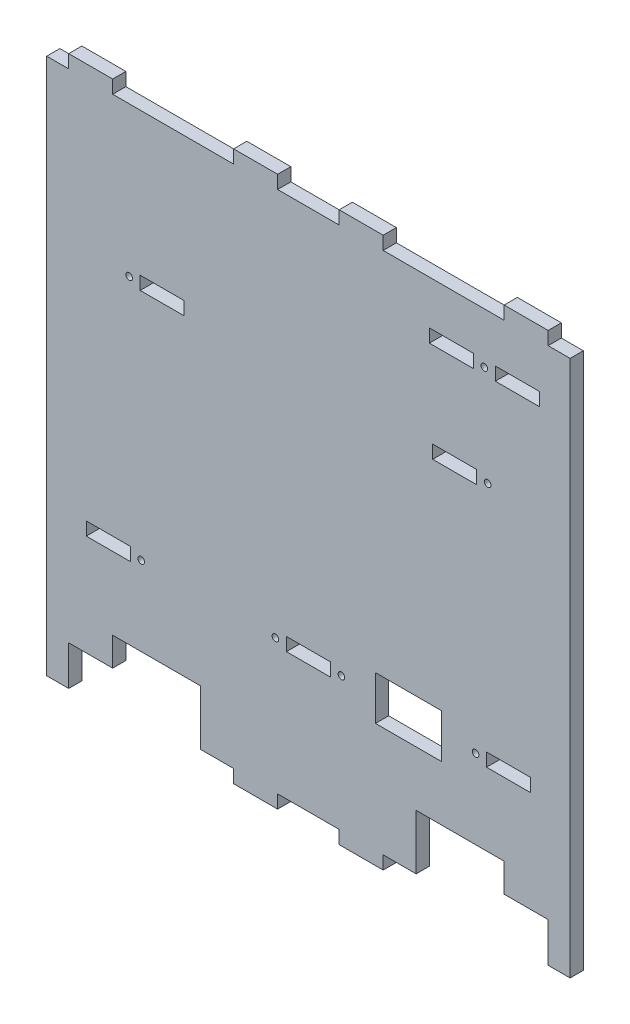
SolidWorks part; units mm, degrees
ref_plane "Plan de face" through (0, 0, 0) normal (0, 0, 1) x (1, 0, 0)
ref_plane "Plan de dessus" through (0, 0, 0) normal (0, 1, 0) x (1, 0, 0)
ref_plane "Plan de droite" through (0, 0, 0) normal (1, 0, 0) x (0, 0, -1)
sketch "Esquisse1" plane through (0, 0, 0) normal (0, 0, 1) x (1, 0, 0)
  line L0 (0, 139.6766) -> (0, -178.3461) construction
  line L1 (-109, 119) -> (109, 119)
  line L2 (-109, 119) -> (-109, -119)
  line L3 (-109, -119) -> (109, -119)
  line L4 (109, 119) -> (109, -119)
  line L5 (-101, -61) -> (-81, -61)
  line L6 (-101, -61) -> (-101, -55)
  line L7 (-101, -55) -> (-81, -55)
  line L8 (-81, -61) -> (-81, -55)
  line L9 (-10, -61) -> (10, -61)
  line L10 (-10, -61) -> (-10, -55)
  line L11 (-10, -55) -> (10, -55)
  line L12 (10, -61) -> (10, -55)
  line L13 (81, -61) -> (101, -61)
  line L14 (81, -61) -> (81, -55)
  line L15 (81, -55) -> (101, -55)
  line L16 (101, -61) -> (101, -55)
  line L17 (-76.5, 54) -> (-56.5, 54)
  line L18 (-76.5, 54) -> (-76.5, 48)
  line L19 (-76.5, 48) -> (-56.5, 48)
  line L20 (-56.5, 54) -> (-56.5, 48)
  line L21 (56.5, 54) -> (76.5, 54)
  line L22 (56.5, 54) -> (56.5, 48)
  line L23 (56.5, 48) -> (76.5, 48)
  line L24 (76.5, 54) -> (76.5, 48)
  line L25 (30.5, -69) -> (60.5, -69)
  line L26 (30.5, -69) -> (30.5, -49)
  line L27 (30.5, -49) -> (60.5, -49)
  line L28 (60.5, -69) -> (60.5, -49)
  line L30 (55, 99) -> (75, 99)
  line L31 (55, 99) -> (55, 93)
  line L32 (55, 93) -> (75, 93)
  line L33 (75, 99) -> (75, 93)
  line L34 (85, 99) -> (105, 99)
  line L35 (85, 99) -> (85, 93)
  line L36 (85, 93) -> (105, 93)
  line L37 (105, 99) -> (105, 93)
  dimension "D1" = 238
  dimension "D2" = 218
  dimension "D3" = 109
  dimension "D4" = 119
  dimension "D5" = 20
  dimension "D6" = 6
  dimension "D7" = 6
  dimension "D8" = 20
  dimension "D9" = 20
  dimension "D10" = 6
  dimension "D11" = 58
  dimension "D12" = 8
  dimension "D13" = 8
  dimension "D14" = 99
  dimension "D15" = 58
  dimension "D16" = 58
  dimension "D17" = 20
  dimension "D18" = 6
  dimension "D19" = 6
  dimension "D20" = 20
  dimension "D21" = 167
  dimension "D22" = 167
  dimension "D23" = 32.5
  dimension "D24" = 32.5
  dimension "D25" = 20
  dimension "D26" = 30
  dimension "D27" = 50
  dimension "D28" = 20.5
  dimension "D29" = 6
  dimension "D30" = 6
  dimension "D31" = 20
  dimension "D32" = 20
  dimension "D33" = 20
  dimension "D34" = 20
  dimension "D35" = 10
  dimension "D36" = 4
extrude "Boss.-Extru.1" add sketch "Esquisse1" along normal blind 6
sketch "Esquisse2" plane through (0, 0, 6) normal (0, 0, 1) x (1, 0, 0)
  line L0 (-109, -119) -> (109, -119) construction
  line L1 (-89, -119) -> (-49, -119)
  line L2 (-89, -119) -> (-89, -94)
  line L3 (-89, -94) -> (-49, -94)
  line L4 (-49, -119) -> (-49, -94)
  line L5 (-109, 119) -> (-109, -119) construction
  line L6 (49, -119) -> (89, -119)
  line L7 (49, -119) -> (49, -94)
  line L8 (49, -94) -> (89, -94)
  line L9 (89, -119) -> (89, -94)
  line L10 (109, -119) -> (109, 119) construction
  dimension "D1" = 40
  dimension "D2" = 20
  dimension "D3" = 40
  dimension "D4" = 20
  dimension "D5" = 25
  dimension "D6" = 25
extrude "Enlèv. mat.-Extru.1" cut sketch "Esquisse2" against normal blind 6
sketch "Esquisse3" plane through (0, 0, 6) normal (0, 0, 1) x (1, 0, 0)
  line L0 (0, 157.5653) -> (0, -190.6765) construction
  line L5 (-49, -119) -> (49, -119) construction
  line L6 (-34, -119) -> (-14, -119)
  line L7 (-34, -119) -> (-34, -125)
  line L8 (-34, -125) -> (-14, -125)
  line L9 (-14, -119) -> (-14, -125)
  line L10 (-49, -119) -> (-49, -94) construction
  line L15 (14, -119) -> (14, -125)
  line L16 (34, -125) -> (14, -125)
  line L17 (34, -119) -> (34, -125)
  line L18 (34, -119) -> (14, -119)
  line L19 (198.2674, 0) -> (-212.4835, 0) construction
  line L20 (0, -157.5653) -> (0, 190.6765) construction
  line L21 (34, 125) -> (14, 125)
  line L22 (14, 119) -> (14, 125)
  line L23 (89, 125) -> (109, 125)
  line L24 (89, 125) -> (89, 119)
  line L25 (89, 119) -> (109, 119)
  line L26 (109, 125) -> (109, 119)
  line L27 (-14, 119) -> (-14, 125)
  line L28 (-34, 125) -> (-14, 125)
  line L29 (-34, 119) -> (-34, 125)
  line L30 (-34, 119) -> (-14, 119)
  line L31 (-109, 125) -> (-109, 119)
  line L32 (-89, 119) -> (-109, 119)
  line L33 (-89, 125) -> (-89, 119)
  line L34 (-89, 125) -> (-109, 125)
  line L35 (34, 119) -> (14, 119)
  line L36 (34, 119) -> (34, 125)
  dimension "D2" = 20
  dimension "D3" = 6
  dimension "D4" = 15
extrude "Boss.-Extru.3" add sketch "Esquisse3" against normal blind 6
sketch "Esquisse4" plane through (0, 0, 6) normal (0, 0, 1) x (1, 0, 0)
  line L0 (-111.0944, 51) -> (126.4062, 51) construction
  line L1 (116.6655, -58) -> (-122.9189, -58) construction
  line L2 (76.5, 48) -> (76.5, 54) construction
  line L3 (0, 153.5677) -> (0, -173.1111) construction
  line L4 (45.0686, 96) -> (109.1297, 96) construction
  line L5 (81, -55) -> (81, -61) construction
  line L6 (10, -61) -> (10, -55) construction
  line L7 (-10, -55) -> (-10, -61) construction
  line L8 (75, 93) -> (75, 99) construction
  line L10 (-56.5, 54) -> (-76.5, 54) construction
  line L13 (55, 93) -> (75, 93) construction
  circle A0 centre (-15, -58) radius 1.5
  circle A1 centre (-76, -58) radius 1.5
  circle A2 centre (80, 96) radius 1.5
  circle A3 centre (81.5, 51) radius 1.5
  circle A4 centre (76, -58) radius 1.5
  circle A5 centre (15, -58) radius 1.5
  circle A6 centre (-81.5, 51) radius 1.5
  dimension "D2" = 5
  dimension "D4" = 3
  dimension "D5" = 5
  dimension "D6" = 5
  dimension "D7" = 3
  dimension "D8" = 3
  dimension "D9" = 3
  dimension "D10" = 5
  dimension "D11" = 3
  dimension "D12" = 5
  dimension "D15" = 3
  dimension "D14" = 3
extrude "Enlèv. mat.-Extru.2" cut sketch "Esquisse4" against normal blind 6
sketch "Esquisse5" plane through (0, 0, 6) normal (0, 0, 1) x (1, 0, 0)
  line L0 (-109, 119) -> (-109, -125)
  line L1 (-109, 119) -> (-119, 119)
  line L2 (-109, -125) -> (-119, -125)
  line L3 (-119, 119) -> (-119, -125)
  line L5 (109, -125) -> (109, 119)
  line L6 (109, -125) -> (119, -125)
  line L7 (109, 119) -> (119, 119)
  line L8 (119, -125) -> (119, 119)
  line L11 (109, 125) -> (89, 125) construction
  line L12 (-89, 125) -> (-109, 125) construction
  dimension "D1" = 10
  dimension "D2" = 10
  dimension "D3" = 244
  dimension "D4" = 244
  dimension "D5" = 6
  dimension "D6" = 6
extrude "Boss.-Extru.4" add sketch "Esquisse5" against normal blind 6
sketch "Esquisse6" plane through (0, 0, 6) normal (0, 0, 1) x (1, 0, 0)
  line L0 (0, 108.4917) -> (0, -172.5759) construction
  line L1 (89, -119) -> (109, -119)
  line L2 (89, -119) -> (89, -107)
  line L3 (89, -107) -> (109, -107)
  line L4 (109, -119) -> (109, -107)
  line L5 (-109, -119) -> (-109, -107)
  line L6 (-89, -107) -> (-109, -107)
  line L7 (-89, -119) -> (-89, -107)
  line L8 (-89, -119) -> (-109, -119)
  dimension "D1" = 12
  dimension "D2" = 20
extrude "Enlèv. mat.-Extru.3" cut sketch "Esquisse6" against normal blind 6
equation "\"D3@Esquisse1\"=\"D2@Esquisse1\"/2"
equation "\"D4@Esquisse1\"=\"D1@Esquisse1\"/2"
